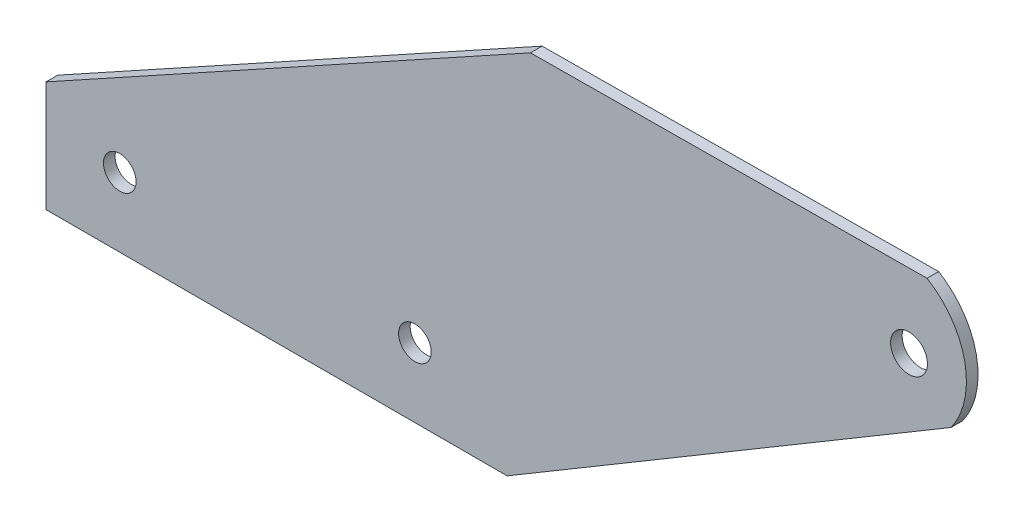
SolidWorks part; units mm, degrees
ref_plane "Front Plane" through (0, 0, 0) normal (0, 0, 1) x (1, 0, 0)
ref_plane "Top Plane" through (0, 0, 0) normal (0, 1, 0) x (1, 0, 0)
ref_plane "Right Plane" through (0, 0, 0) normal (1, 0, 0) x (0, 0, -1)
sketch "Sketch1" plane through (0, 0, 0) normal (0, 0, 1) x (1, 0, 0)
  line L0 (0, 0) -> (0, 15.24)
  line L1 (0, 15.24) -> (66.7136, 52.0603)
  line L2 (0, 0) -> (63.5, 0)
  line L3 (0.8801, 0) -> (-0.8801, 0) construction
  line L4 (66.7136, 52.0603) -> (121.3236, 52.4827)
  line L7 (124.6348, 36.3399) -> (63.5, 0)
  circle A2 centre (10.16, 9.525) radius 2.2479
  circle A3 centre (50.8, 9.525) radius 2.2479
  circle A5 centre (118.8416, 42.3032) radius 2.54
  arc A6 (121.3236, 52.4827) -> (124.6348, 36.3399) centre (115.5579, 42.889) cw
  dimension "D9" = 5.08
  dimension "D11" = 4.4958
  dimension "D12" = 9.525
  dimension "D13" = 10.16
  dimension "D14" = 4.4958
  dimension "D15" = 40.64
  dimension "D16" = 9.525
  dimension "D2" = 63.5
  dimension "D3" = 15.24
  dimension "D4" = 76.2
  dimension "D5" = 71.12
  dimension "D6" = 54.61
  dimension "D10" = 10.16
extrude "Boss-Extrude1" add sketch "Sketch1" against normal blind 1.6002
